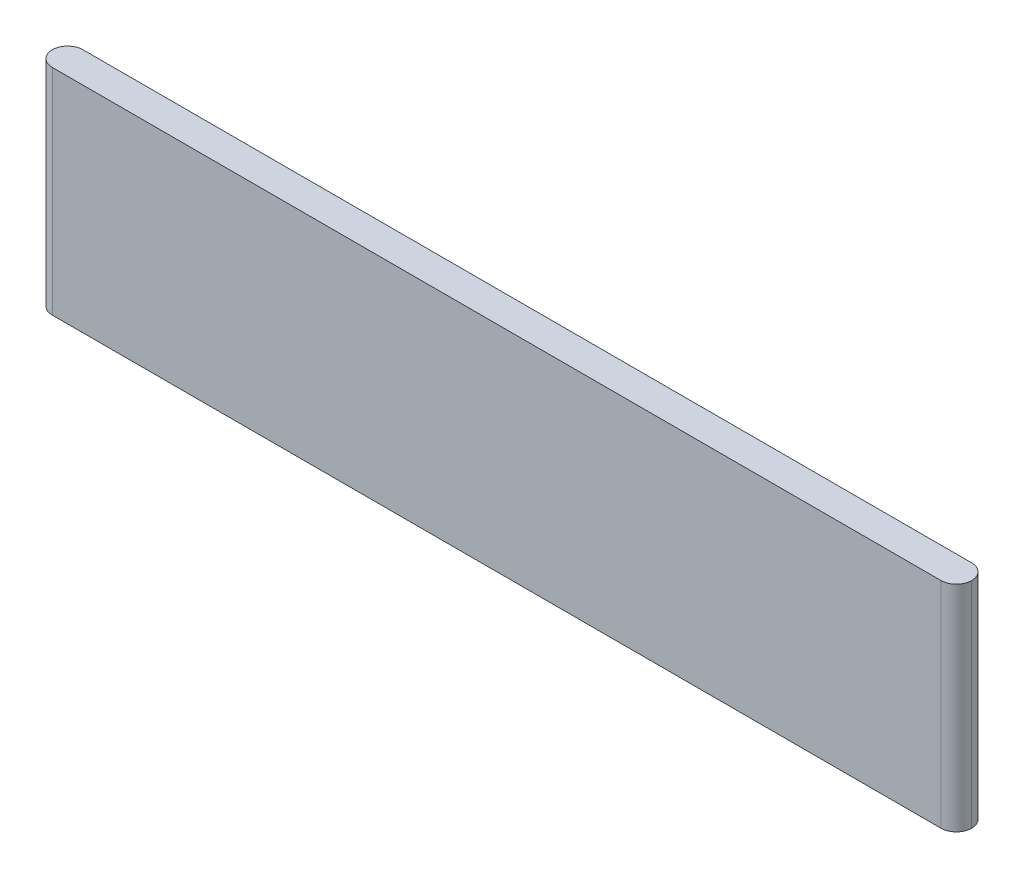
SolidWorks part; units mm, degrees
ref_plane "Front Plane" through (0, 0, 0) normal (0, 0, 1) x (1, 0, 0)
ref_plane "Top Plane" through (0, 0, 0) normal (0, 1, 0) x (1, 0, 0)
ref_plane "Right Plane" through (0, 0, 0) normal (1, 0, 0) x (0, 0, -1)
sketch "Sketch1" plane through (0, 0, 0) normal (0, 1, 0) x (1, 0, 0)
  line L1 (-750, -175) -> (750, -175)
  line L2 (-750, -175) -> (-750, 175)
  line L3 (-750, 175) -> (750, 175)
  line L4 (750, -175) -> (750, 175)
  line L5 (-750, -175) -> (750, 175) construction
  line L6 (-750, 175) -> (750, -175) construction
  point P0 (0, 0)
  dimension "D1" = 1500
  dimension "D2" = 350
extrude "Boss-Extrude1" add sketch "Sketch1" along normal blind 50
fillet "Fillet1" radius 25 4 edges at (750, 0, 0) (750, 50, 0) (-750, 0, 0) (-750, 50, 0)
move or copy body "Body-Move/Copy1" bodies to move or copy 101 copy no rotation origin (0, 0, 0) rotation axis (1, 0, 0) rotation angle 90
